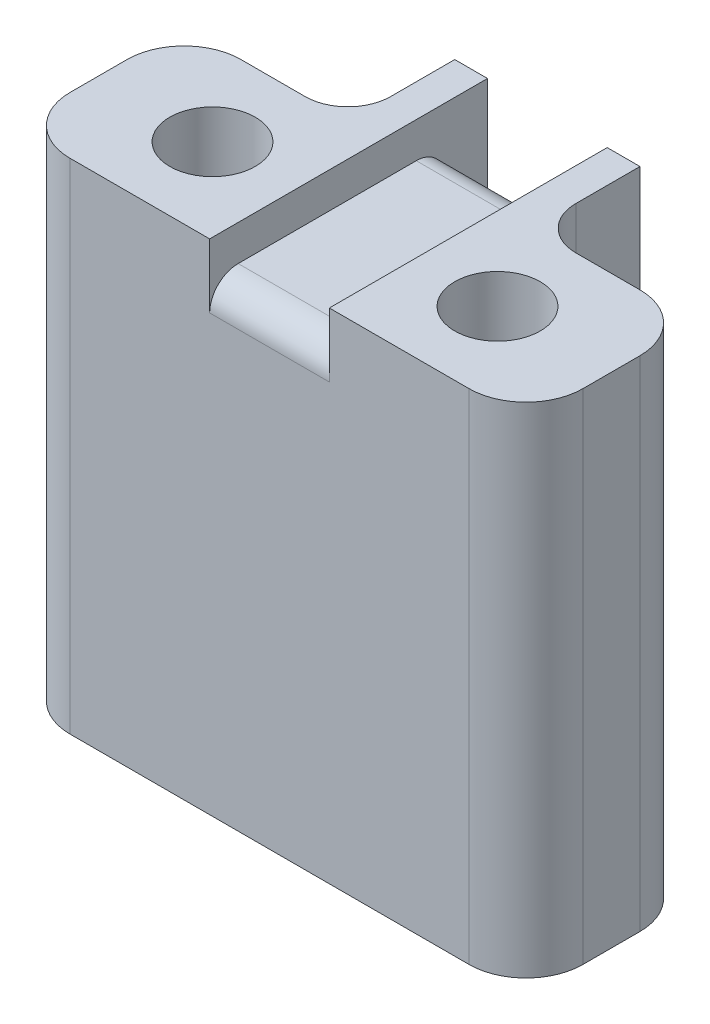
SolidWorks part; units mm, degrees
ref_plane "Front Plane" through (0, 0, 0) normal (0, 0, 1) x (1, 0, 0)
ref_plane "Top Plane" through (0, 0, 0) normal (0, 1, 0) x (1, 0, 0)
ref_plane "Right Plane" through (0, 0, 0) normal (1, 0, 0) x (0, 0, -1)
sketch "Sketch1" plane through (0, 0, 0) normal (0, 1, 0) x (1, 0, 0)
  line L1 (-9, -3) -> (9, -3)
  line L2 (-9, -3) -> (-9, 3)
  line L3 (-9, 3) -> (9, 3)
  line L4 (9, -3) -> (9, 3)
  line L5 (-9, -3) -> (9, 3) construction
  line L6 (-9, 3) -> (9, -3) construction
  point P0 (0, 0)
  dimension "D1" = 6
  dimension "D2" = 18
extrude "Boss-Extrude1" add sketch "Sketch1" along normal blind 17.5
sketch "Sketch2" plane through (0, 17.5, 0) normal (0, 1, 0) x (1, 0, 0)
  line L0 (5, 0) -> (-5, 0)
  line L1 (0, -1.1551) -> (0, 1.1551)
  circle A0 centre (-5, 0) radius 1.5
  circle A1 centre (5, 0) radius 1.5
  point P4 (0, 0)
  point P8 (0, 0)
extrude "Cut-Extrude1" cut sketch "Sketch2" against normal through all contours A0 | A1
fillet "Fillet1" radius 2 4 edges at (-9, 8.75, 3) (9, 8.75, 3) (9, 8.75, -3) (-9, 8.75, -3)
sketch "Sketch3" plane through (0, 0, -3) normal (0, 0, -1) x (-1, 0, 0)
  line L0 (0, 17.5) -> (0, 16)
  line L1 (-7, 17.5) -> (7, 17.5) construction
  line L7 (-0.9557, 14.2479) -> (3, 21.5) construction
  line L8 (-3, 21.5) -> (-0.2484, 16.4554) construction
  line L9 (-3.25, 13) -> (3.25, 13)
  line L10 (-3.25, 13) -> (-3.25, 19)
  line L11 (-3.25, 19) -> (3.25, 19)
  line L12 (3.25, 13) -> (3.25, 19)
  line L13 (-3.25, 13) -> (3.25, 19) construction
  line L14 (-3.25, 19) -> (3.25, 13) construction
  line L15 (-2.1, 13.5) -> (2.1, 13.5)
  line L16 (-2.1, 13.5) -> (-2.1, 18.5)
  line L17 (-2.1, 18.5) -> (2.1, 18.5)
  line L18 (2.1, 13.5) -> (2.1, 18.5)
  line L19 (-2.1, 13.5) -> (2.1, 18.5) construction
  line L20 (-2.1, 18.5) -> (2.1, 13.5) construction
  line M1 (7, 17.5) -> (-7, 17.5)
  dimension "D1" = 1.5
  dimension "D2" = 6
  dimension "D3" = 5
  dimension "6" = 6
  dimension "D4" = 6.5
extrude "Boss-Extrude2" add sketch "Sketch3" along normal blind 3.75 contours L9 L12 L10 M1 region at (3.1709, 15.25, -3)
sketch "Sketch4" plane through (0, 0, -3) normal (0, 0, -1) x (-1, 0, 0)
  line L4 (-2.1, 17.5) -> (-2.1, 13.5)
  line L5 (-2.1, 13.5) -> (2.1, 13.5)
  line L6 (2.1, 13.5) -> (2.1, 17.5)
  line L7 (2.1, 17.5) -> (-2.1, 17.5)
extrude "Boss-Extrude3" add sketch "Sketch4" along normal blind 2.25
sketch "Sketch5" plane through (0, 17.5, 0) normal (0, 1, 0) x (1, 0, 0)
  line L0 (-2.1, 5.25) -> (-2.1, -3)
  line L1 (-7, -3) -> (7, -3) construction
  line L2 (2.1, 5.25) -> (2.1, -3)
  line M4 (-7, -3) -> (7, -3)
  line M12 (2.1, 5.25) -> (-2.1, 5.25)
extrude "Cut-Extrude2" cut sketch "Sketch5" against normal blind 1.25 contours L2 L0 M12 M4 region at (0, 17.5, -1.125)
fillet "Fillet5" radius 1 2 edges at (0, 16.25, 3) (0, 16.25, -5.25)
fillet "Fillet6" radius 1.5 3 edges at (-3.25, 15.25, -3) (3.25, 15.25, -3) (0, 13, -3)
fillet "Fillet7" radius 0.75 1 edges at (0, 13, -6.75)
